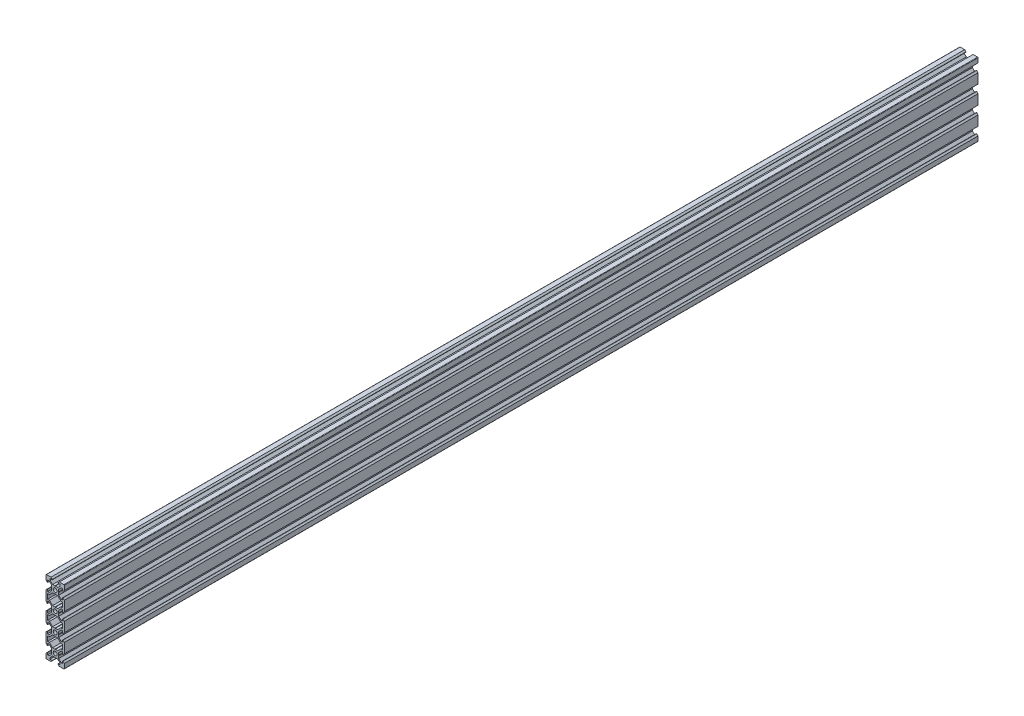
SolidWorks part; units mm, degrees
ref_plane "Plan de face" through (0, 0, 0) normal (0, 0, 1) x (1, 0, 0)
ref_plane "Plan de dessus" through (0, 0, 0) normal (0, 1, 0) x (1, 0, 0)
ref_plane "Plan de droite" through (0, 0, 0) normal (1, 0, 0) x (0, 0, -1)
ref_axis "Axe" through (0, 0, -13.782) along (0, 0, 1)
sketch "Esquisse1" plane through (0, 0, 0) normal (0, 0, 1) x (1, 0, 0)
  line L0 (0, 27.6392) -> (0, -27.6392) construction
  line L1 (-33.6074, 0) -> (33.6074, 0) construction
  line L2 (0, 0) -> (-22.2114, 22.2114) construction
  line L3 (-9.5, 10) -> (-4.58, 10)
  line L4 (-4.58, 10) -> (-3.125, 8.545)
  line L5 (-3.125, 8.545) -> (-3.125, 8.2)
  line L6 (-3.125, 8.2) -> (-5.5, 8.2)
  line L7 (-2.8393, 3.9) -> (-5.5, 6.5607)
  line L8 (-2.8393, 3.9) -> (-0.21, 3.9)
  line L9 (-5.5, 6.5607) -> (-5.5, 8.2)
  line L10 (0, 3.69) -> (0, 2.1)
  line L11 (-3.9, 2.8393) -> (-6.5607, 5.5)
  line L12 (-8.545, 3.125) -> (-8.2, 3.125)
  line L13 (-8.2, 3.125) -> (-8.2, 5.5)
  line L14 (-6.5607, 5.5) -> (-8.2, 5.5)
  line L15 (-10, 4.58) -> (-8.545, 3.125)
  line L16 (-10, 9.5) -> (-10, 4.58)
  line L17 (-0.21, 3.9) -> (0, 3.69)
  line L18 (-3.9, 2.8393) -> (-3.9, 0.21)
  line L19 (-6.2393, -12.7) -> (-8.2, -12.7)
  line L20 (-3.9, 0.21) -> (-3.69, 0)
  line L21 (-0.21, -3.9) -> (0, -3.69)
  line L22 (0, -3.69) -> (0, -2.1)
  line L23 (-6.5607, -5.5) -> (-8.2, -5.5)
  line L24 (-2.8393, -3.9) -> (-0.21, -3.9)
  line L25 (-8.545, -3.125) -> (-8.2, -3.125)
  line L26 (-10, -4.58) -> (-8.545, -3.125)
  line L27 (-8.2, -3.125) -> (-8.2, -5.5)
  line L28 (-2.8393, -3.9) -> (-6.2393, -7.3)
  line L29 (-3.9, -2.8393) -> (-6.5607, -5.5)
  line L30 (-3.9, -2.8393) -> (-3.9, -0.21)
  line L31 (-3.9, -0.21) -> (-3.69, 0)
  line L32 (-6.2393, -7.3) -> (-8.2, -7.3)
  line L33 (-8.2, -7.3) -> (-8.2, -12.7)
  line L34 (-8.2, -10) -> (-10, -10) construction
  line L35 (-10, -15.42) -> (-10, -4.58)
  line L36 (-3.9, -19.79) -> (-3.69, -20)
  line L37 (-3.9, -17.1607) -> (-3.9, -19.79)
  line L38 (-3.9, -17.1607) -> (-6.5607, -14.5)
  line L39 (-2.8393, -16.1) -> (-6.2393, -12.7)
  line L40 (-8.2, -16.875) -> (-8.2, -14.5)
  line L41 (-10, -15.42) -> (-8.545, -16.875)
  line L42 (-8.545, -16.875) -> (-8.2, -16.875)
  line L43 (-2.8393, -16.1) -> (-0.21, -16.1)
  line L44 (-6.5607, -14.5) -> (-8.2, -14.5)
  line L45 (0, -16.31) -> (0, -17.9)
  line L46 (-0.21, -16.1) -> (0, -16.31)
  line L47 (-8.2, -30) -> (-10, -30) construction
  line L48 (-3.69, -20) -> (0, -20) construction
  line L49 (-0.21, -23.9) -> (0, -23.69)
  line L50 (0, -23.69) -> (0, -22.1)
  line L51 (-6.5607, -25.5) -> (-8.2, -25.5)
  line L52 (-2.8393, -23.9) -> (-0.21, -23.9)
  line L53 (-8.545, -23.125) -> (-8.2, -23.125)
  line L54 (-10, -24.58) -> (-8.545, -23.125)
  line L55 (-8.2, -23.125) -> (-8.2, -25.5)
  line L56 (-2.8393, -23.9) -> (-6.2393, -27.3)
  line L57 (-3.9, -22.8393) -> (-6.5607, -25.5)
  line L58 (-3.9, -22.8393) -> (-3.9, -20.21)
  line L59 (-3.9, -20.21) -> (-3.69, -20)
  line L60 (-10, -24.58) -> (-10, -35.42)
  line L61 (-8.2, -32.7) -> (-8.2, -27.3)
  line L62 (-3.69, -40) -> (0, -40) construction
  line L63 (-8.2, -50) -> (-10, -50) construction
  line L64 (0, -60) -> (-22.2114, -82.2114) construction
  line L65 (-33.6074, -60) -> (33.6074, -60) construction
  line L66 (0, -87.6392) -> (0, -32.3608) construction
  line L67 (-6.2393, -32.7) -> (-8.2, -32.7)
  line L68 (-3.9, -39.79) -> (-3.69, -40)
  line L69 (-3.9, -37.1607) -> (-3.9, -39.79)
  line L70 (-3.9, -37.1607) -> (-6.5607, -34.5)
  line L71 (-2.8393, -36.1) -> (-6.2393, -32.7)
  line L72 (-8.2, -36.875) -> (-8.2, -34.5)
  line L73 (-10, -35.42) -> (-8.545, -36.875)
  line L74 (-8.545, -36.875) -> (-8.2, -36.875)
  line L75 (-6.2393, -27.3) -> (-8.2, -27.3)
  line L76 (-2.8393, -36.1) -> (-0.21, -36.1)
  line L77 (-6.5607, -34.5) -> (-8.2, -34.5)
  line L78 (0, -36.31) -> (0, -37.9)
  line L79 (-0.21, -36.1) -> (0, -36.31)
  line L80 (-0.21, -43.9) -> (0, -43.69)
  line L81 (0, -43.69) -> (0, -42.1)
  line L82 (-6.5607, -45.5) -> (-8.2, -45.5)
  line L83 (-2.8393, -43.9) -> (-0.21, -43.9)
  line L84 (-8.545, -43.125) -> (-8.2, -43.125)
  line L85 (-10, -44.58) -> (-8.545, -43.125)
  line L86 (-8.2, -43.125) -> (-8.2, -45.5)
  line L87 (-2.8393, -43.9) -> (-6.2393, -47.3)
  line L88 (-3.9, -42.8393) -> (-6.5607, -45.5)
  line L89 (-3.9, -42.8393) -> (-3.9, -40.21)
  line L90 (-3.9, -40.21) -> (-3.69, -40)
  line L91 (-10, -44.58) -> (-10, -55.42)
  line L92 (-8.2, -52.7) -> (-8.2, -47.3)
  line L93 (-6.2393, -52.7) -> (-8.2, -52.7)
  line L94 (-3.9, -59.79) -> (-3.69, -60)
  line L95 (-3.9, -57.1607) -> (-3.9, -59.79)
  line L96 (-3.9, -57.1607) -> (-6.5607, -54.5)
  line L97 (-2.8393, -56.1) -> (-6.2393, -52.7)
  line L98 (-8.2, -56.875) -> (-8.2, -54.5)
  line L99 (-10, -55.42) -> (-8.545, -56.875)
  line L100 (-8.545, -56.875) -> (-8.2, -56.875)
  line L101 (-2.8393, -56.1) -> (-0.21, -56.1)
  line L102 (-6.5607, -54.5) -> (-8.2, -54.5)
  line L103 (0, -56.31) -> (0, -57.9)
  line L104 (-0.21, -56.1) -> (0, -56.31)
  line L105 (-3.9, -60.21) -> (-3.69, -60)
  line L106 (-6.2393, -47.3) -> (-8.2, -47.3)
  line L107 (-3.9, -62.8393) -> (-3.9, -60.21)
  line L108 (-0.21, -63.9) -> (0, -63.69)
  line L109 (-10, -69.5) -> (-10, -64.58)
  line L110 (-10, -64.58) -> (-8.545, -63.125)
  line L111 (-6.5607, -65.5) -> (-8.2, -65.5)
  line L112 (-8.2, -63.125) -> (-8.2, -65.5)
  line L113 (-8.545, -63.125) -> (-8.2, -63.125)
  line L114 (-3.9, -62.8393) -> (-6.5607, -65.5)
  line L115 (0, -63.69) -> (0, -62.1)
  line L116 (-5.5, -66.5607) -> (-5.5, -68.2)
  line L117 (-2.8393, -63.9) -> (-0.21, -63.9)
  line L118 (-2.8393, -63.9) -> (-5.5, -66.5607)
  line L119 (-3.125, -68.2) -> (-5.5, -68.2)
  line L120 (-3.125, -68.545) -> (-3.125, -68.2)
  line L121 (-4.58, -70) -> (-3.125, -68.545)
  line L122 (-9.5, -70) -> (-4.58, -70)
  arc A0 (0, -2.1) -> (0, 2.1) centre (0, 0) cw
  arc A1 (-9.5, 10) -> (-10, 9.5) centre (-9.5, 9.5) ccw
  arc A2 (0, -42.1) -> (0, -37.9) centre (0, -40) cw
  arc A3 (-9.5, -70) -> (-10, -69.5) centre (-9.5, -69.5) cw
  arc A4 (0, -17.9) -> (0, -22.1) centre (0, -20) ccw
  arc A5 (0, -57.9) -> (0, -62.1) centre (0, -60) ccw
  point P4 (0, 0)
  point P7 (0, 0)
  point P30 (-10, 10)
  point P60 (0, -20)
  point P146 (-10, -70)
  dimension "D5" = 11
  dimension "D2" = 2.1
  dimension "D3" = 6.25
  dimension "D10" = 0.5
  dimension "D4" = 9.16
  dimension "D6" = 1.5
  dimension "D7" = 1.8
  dimension "D8" = 4.3
  dimension "D9" = 20
  dimension "D11" = 0.42
  dimension "D12" = 10
  dimension "D13" = 1.8
extrude "Boss.-Extru.1" add sketch "Esquisse1" along normal blind 1000
sketch "Esquisse3" plane through (0, 0, 1000) normal (0, 0, 1) x (1, 0, 0)
  line L0 (0, 0) -> (-9.8536, 9.8536) construction
  line L1 (-8.2, 8.2) -> (-8.2, 6.57)
  line L2 (-8.2, 6.57) -> (-7.54, 6.57)
  line L3 (-7.54, 6.57) -> (-6.57, 7.54)
  line L4 (-8.2, 3.125) -> (-8.2, 5.5) construction
  line L5 (-6.57, 8.2) -> (-6.57, 7.54)
  line L6 (-8.2, 8.2) -> (-6.57, 8.2)
  line L7 (-5.5, 6.5607) -> (-5.5, 8.2) construction
  line L8 (-10, -30) -> (6.918, -30) construction
  line L9 (-10, -24.58) -> (-10, -35.42) construction
  line L10 (-8.2, -68.2) -> (-6.57, -68.2)
  line L11 (-6.57, -68.2) -> (-6.57, -67.54)
  line L12 (-7.54, -66.57) -> (-6.57, -67.54)
  line L13 (-8.2, -66.57) -> (-7.54, -66.57)
  line L14 (-8.2, -68.2) -> (-8.2, -66.57)
  arc A0 (-9.5, 10) -> (-10, 9.5) centre (-9.5, 9.5) ccw construction
  point P13 (-7.055, 7.055)
  point P14 (-6.57, 7.87)
  point P26 (-7.055, -67.055)
  dimension "D1" = 1.07
extrude "Enlèv. mat.-Extru.1" [suppressed] cut sketch "Esquisse3" against normal through all
mirror "Symétrie1" of "Enlèv. mat.-Extru.1", "Boss.-Extru.1"
